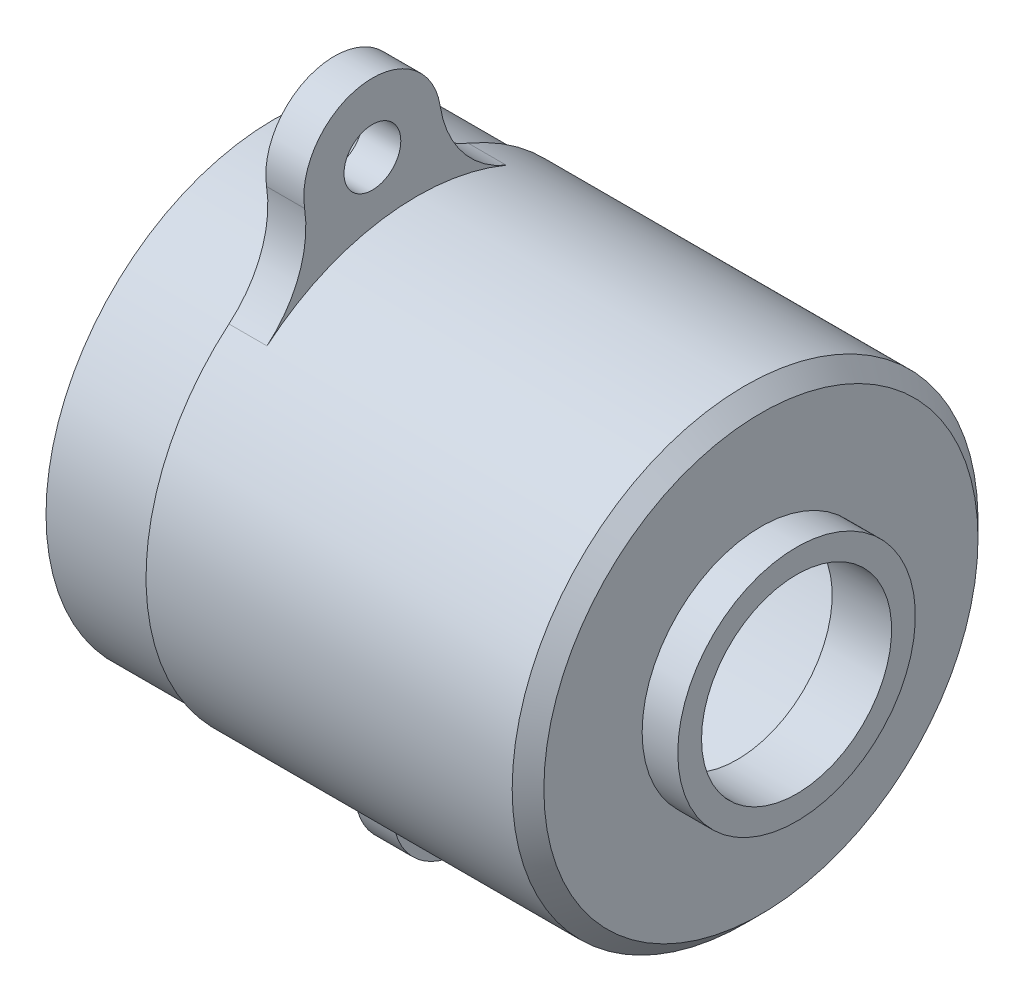
SolidWorks part; units mm, degrees
material "6061-T6 (SS)"
ref_plane "Front Plane" through (0, 0, 0) normal (0, 0, 1) x (1, 0, 0)
ref_plane "Top Plane" through (0, 0, 0) normal (0, 1, 0) x (1, 0, 0)
ref_plane "Right Plane" through (0, 0, 0) normal (1, 0, 0) x (0, 0, -1)
other "Center of Mass"
sketch "Sketch1" plane through (-25.4, 0, 0) normal (1, 0, 0) x (0, 0, -1)
  line L0 (0, 0) -> (-2.9763, 19.3027) construction
  line L1 (-0.1069, 15.7295) -> (1.5529, 20.0011) construction
  line L2 (1.5529, 20.0011) -> (-1.3165, 23.5743) construction
  line L3 (-1.3165, 23.5743) -> (-5.8456, 22.876) construction
  line L4 (-5.8456, 22.876) -> (-7.5055, 18.6044) construction
  line L5 (-7.5055, 18.6044) -> (-4.6361, 15.0312) construction
  line L6 (-4.6361, 15.0312) -> (-0.1069, 15.7295) construction
  line L7 (4.6361, -15.0312) -> (0.1069, -15.7295) construction
  line L8 (0.1069, -15.7295) -> (-1.5529, -20.0011) construction
  line L9 (-1.5529, -20.0011) -> (1.3165, -23.5743) construction
  line L10 (1.3165, -23.5743) -> (5.8456, -22.876) construction
  line L11 (5.8456, -22.876) -> (7.5055, -18.6044) construction
  line L12 (7.5055, -18.6044) -> (4.6361, -15.0312) construction
  line L13 (-7.5055, 18.6044) -> (1.5529, 20.0011) construction
  line L15 (0, 0) -> (12.0783, 1.8623) construction
  circle A0 centre (0, 0) radius 13.9746
  circle A1 centre (0, 0) radius 15.5621 construction
  circle A3 centre (2.9763, -19.3027) radius 3.9688 construction
  circle A4 centre (-2.9763, 19.3027) radius 8.6983 construction
  arc A8 (-10.0197, 11.9073) -> (-5.9677, -14.3724) centre (0, 0) ccw
  arc A9 (5.9677, 14.3724) -> (10.0197, -11.9073) centre (0, 0) cw
  circle A16 centre (-2.9763, 19.3027) radius 2.667 construction
  circle A17 centre (2.9763, -19.3027) radius 2.667 construction
  arc A18 (-9.5936, 36.4443) -> (-11.4452, 22.7071) centre (127.7924, 10.9323) ccw construction
  arc A19 (4.413, 36.4443) -> (4.5624, 28.8025) centre (76.8178, 34.0373) ccw construction
  arc A20 (-10.0197, 11.9073) -> (-7.5055, 18.6044) centre (-14.7192, 17.4921) ccw
  arc A21 (-7.5055, 18.6044) -> (1.5529, 20.0011) centre (-2.9763, 19.3027) cw
  arc A22 (1.5529, 20.0011) -> (5.9677, 14.3724) centre (8.7667, 21.1134) ccw
  arc A23 (7.5055, -18.6044) -> (10.0197, -11.9073) centre (14.7192, -17.4921) cw
  arc A24 (-1.5529, -20.0011) -> (7.5055, -18.6044) centre (2.9763, -19.3027) ccw
  arc A25 (-5.9677, -14.3724) -> (-1.5529, -20.0011) centre (-8.7667, -21.1134) cw
  point P4 (-2.3715, 15.3803)
  dimension "D1" = 27.9492
  dimension "D4" = 5.334
  dimension "D2" = 1.5875
  dimension "D3" = 7.9375
extrude "Boss-Extrude1" add sketch "Sketch1" along normal blind 2.54
sketch "Sketch2" plane through (-22.86, 0, 0) normal (1, 0, 0) x (0, 0, -1)
  circle A0 centre (0, 0) radius 13.9746
  circle A1 centre (0, 0) radius 15.5621
  arc A2 (-10.0197, 11.9073) -> (-5.9677, -14.3724) centre (0, 0) ccw construction
  circle A3 centre (0, 0) radius 13.9746 construction
extrude "Boss-Extrude2" add sketch "Sketch2" along normal up to surface (21.3975 mm away)
sketch "Sketch5" plane through (0, 0, 0) normal (0, 0, 1) x (1, 0, 0)
  line L1 (2.5063, 7.9375) -> (2.5063, 6.35)
  line L3 (-1.4625, -15.5621) -> (-1.4625, 15.5621) construction
  line L4 (-1.4625, 6.35) -> (-1.4625, 15.5621)
  line L5 (0, 0) -> (45.5597, 0) construction
  line L6 (-1.4625, 6.35) -> (2.5063, 6.35)
  line L9 (2.5063, 7.9375) -> (0.125, 7.9375)
  line L10 (0.125, 7.9375) -> (0.125, 14.5038)
  line L12 (0.125, 14.5038) -> (-0.9333, 15.5621)
  line L13 (-0.9333, 15.5621) -> (-1.4625, 15.5621)
  line L14 (-1.4625, 13.9746) -> (-0.4042, 15.0329) construction
  dimension "D2" = 3.9688
  dimension "D1" = 12.7
  dimension "D3" = 1.5875
  dimension "D4" = 1.5875
revolve "Revolve1" add sketch "Sketch5" angle 360 about L5
sketch "Sketch3" plane through (-25.4, 0, 0) normal (-1, 0, 0) x (0, 0, 1)
  circle A0 centre (0, 0) radius 13.9746
  circle A1 centre (0, 0) radius 15.2446
  circle A2 centre (0, 0) radius 13.9746 construction
  dimension "D1" = 1.27
extrude "Boss-Extrude3" add sketch "Sketch3" along normal blind 7
sketch "Sketch6" plane through (0, 0, 0) normal (0, 0, 1) x (1, 0, 0)
  line L0 (-25.4, -23.8855) -> (-25.2167, -23.8855)
  line L1 (-25.4, -23.8855) -> (-22.86, -23.8855) construction
  line L2 (-25.4, -23.8855) -> (-25.4, -25.4)
  line L3 (-25.4, -18.6044) -> (-25.4, -23.8855) construction
  arc A0 (-25.4, -25.4) -> (-25.087, -27.369) centre (-19.05, -25.4) ccw construction
  arc A1 (-25.2167, -23.8855) -> (-25.4, -25.4) centre (-19.05, -25.4) cw
extrude "Cut-Extrude1" [suppressed] cut sketch "Sketch6" against normal through all both and the other way through all
hole_wizard "#6 Clearance Hole1" positions "Sketch7" profile "Sketch8" hole size "#6" standard "ANSI Inch" end condition up to next
sketch "Sketch7" plane through (-22.86, 0, 0) normal (1, 0, 0) x (0, 0, -1)
  point P0 (-2.9763, 19.3027)
  point P3 (2.9763, -19.3027)
sketch "Sketch8" plane through (-22.86, 19.3027, 2.9763) normal (0, 1, 0) x (0, 0, -1)
  line L0 (0, 0) -> (0, 2.54)
  line L1 (0, 2.54) -> (1.8986, 2.54)
  line L2 (1.8986, 2.54) -> (1.8986, 0)
  line L5 (1.8986, 0) -> (0, 0)
  line L11 (0, -6.35) -> (0, 107.95) construction
  dimension "Thru Hole Dia." = 3.7973
  dimension "Thru Hole Depth" = 2.54
equation "\"motor diameter\"= 28mm"
equation "\"D1@Sketch1\"=\"motor diameter\"-0.002in"
equation "\"D1@Boss-Extrude3\"=7mm"
equation "\"D2@Sketch5\"=5/32"
